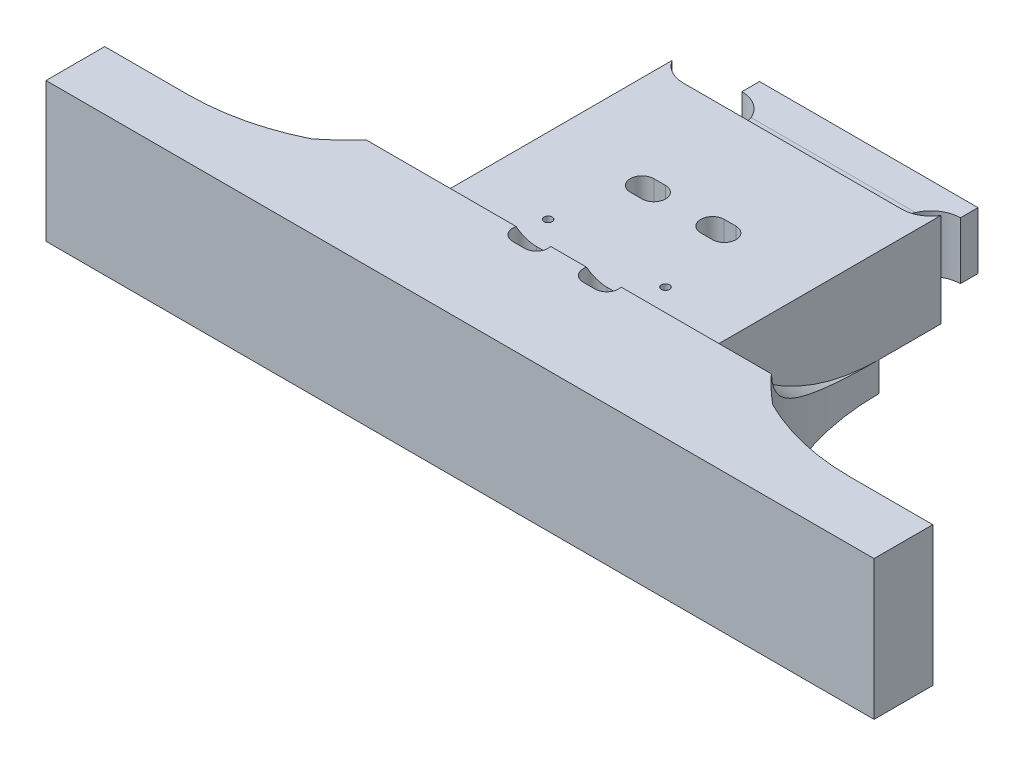
SolidWorks part; units mm, degrees
ref_plane "Front Plane" through (0, 0, 0) normal (0, 0, 1) x (1, 0, 0)
ref_plane "Top Plane" through (0, 0, 0) normal (0, 1, 0) x (1, 0, 0)
ref_plane "Right Plane" through (0, 0, 0) normal (1, 0, 0) x (0, 0, -1)
sketch "Sketch2" plane through (0, 0, 138.6086) normal (0, 0, 1) x (1, 0, 0)
  line L0 (70.4445, 0) -> (70.4445, 5) construction
  line L1 (-70.5526, 0) -> (70.4445, 0)
  line L2 (-70.5526, 0) -> (-70.5526, 23.7194)
  line L3 (-70.5526, 23.7194) -> (70.4445, 23.7194)
  line L4 (70.4445, 0) -> (70.4445, 23.7194)
extrude "Boss-Extrude1" add sketch "Sketch2" along normal blind 40
sketch "Sketch3" plane through (-70.5526, 0, 0) normal (-1, 0, 0) x (0, 0, 1)
  line L0 (138.6086, 23.7194) -> (138.6086, 0) construction
  line L3 (138.6086, 5) -> (152.3731, 5)
  line L4 (178.6086, 23.7194) -> (138.6086, 23.7194) construction
  line L5 (158.6086, 23.7194) -> (178.6086, 23.7194)
  line L8 (138.6086, 23.7194) -> (138.6086, 0)
  line L9 (138.6086, 0) -> (178.6086, 0)
  line L10 (178.6086, 0) -> (178.6086, 23.7194)
  line L11 (178.6086, 23.7194) -> (138.6086, 23.7194)
  line L12 (138.6086, 23.7194) -> (138.6086, 0)
  line L13 (138.6086, 0) -> (178.6086, 0)
  line L14 (178.6086, 0) -> (178.6086, 23.7194)
  line L15 (178.6086, 23.7194) -> (138.6086, 23.7194)
  arc A0 (138.6086, 5) -> (168.6086, 23.7194) centre (138.6086, 38.399) ccw
  point P2 (158.6086, 23.7194)
  point P21 (168.6086, 23.7194)
  line M6 (138.6086, 23.7194) -> (138.6086, 0)
  line M9 (178.6086, 23.7194) -> (138.6086, 23.7194)
  dimension "D2" = 5
  dimension "D3" = 23.7194
  dimension "D1" = 0
extrude "Cut-Extrude1" cut sketch "Sketch3" against normal through all contours M6 M9 region at (-70.5526, 16.0164, 150.4428)
sketch "Sketch4" plane through (0, 5, 0) normal (0, 1, 0) x (1, 0, 0)
  line L0 (-0.0541, -138.6086) -> (-0.0541, -183.6086)
  line L1 (70.4445, -138.6086) -> (-70.5526, -138.6086) construction
  line L2 (70.4445, -168.6086) -> (-70.5526, -168.6086) construction
  line L4 (-22.9249, -168.6086) -> (-22.9249, -128.1086)
  line L9 (-0.6345, -168.6086) -> (0.8576, -168.6086) construction
  line L10 (22.8168, -168.6086) -> (-22.9249, -168.6086)
  line L11 (22.8168, -168.6086) -> (22.8168, -128.1086)
  line L15 (-18.6541, -120.5086) -> (-18.6541, -117.5086)
  line L16 (-0.0541, -138.6086) -> (-0.0541, -118.0787) construction
  line L17 (-18.6541, -117.5086) -> (18.5459, -117.5086)
  line L19 (18.5459, -120.5086) -> (18.5459, -117.5086)
  circle A5 centre (18.5459, -125.5086) radius 5 construction
  arc A7 (18.5459, -120.5086) -> (22.8168, -128.1086) centre (18.5459, -125.5086) ccw
  circle A9 centre (-18.6541, -125.5086) radius 5
  arc A10 (-22.9249, -128.1086) -> (-18.6541, -120.5086) centre (-18.6541, -125.5086) ccw
  circle A11 centre (18.5459, -125.5086) radius 5
  arc A12 (18.5459, -120.5086) -> (22.8168, -128.1086) centre (18.5459, -125.5086) ccw
  point P31 (-0.0541, -117.5086)
  line M11 (-13.4387, -138.6086) -> (13.3306, -138.6086)
  arc M12 (13.3306, -138.6086) -> (8.0264, -116.1199) centre (18.5459, -125.5086) cw
  dimension "D3" = 3
  dimension "D1" = 0
  dimension "D4" = 0
extrude "Boss-Extrude2" add sketch "Sketch4" along normal blind 16 contours L17 M11 M12 | A7 L19 L17 L0 L10 L11 M12 M11 | A10 L4 L10 L0 L17 L15 M11 region at (11.7773, 5, 146.7916) region at (-9.2774, 5, 142.9696)
sketch "Sketch6" plane through (0, 23.7194, 0) normal (0, 1, 0) x (1, 0, 0)
  line L0 (-18.6541, -130.5086) -> (18.5459, -130.5086)
  line L1 (18.5459, -120.5086) -> (18.5459, -117.5086) construction
  line L2 (-18.6541, -117.5086) -> (18.5459, -117.5086) construction
  line L3 (-18.6541, -120.5086) -> (-18.6541, -117.5086) construction
  line L4 (18.5459, -117.5086) -> (18.5459, -120.5086)
  line L5 (-18.6541, -117.5086) -> (-18.6541, -120.5086)
  line L6 (18.5459, -117.5086) -> (-18.6541, -117.5086)
  arc A2 (18.5459, -120.5086) -> (22.8168, -128.1086) centre (18.5459, -125.5086) ccw construction
  arc A3 (-22.9249, -128.1086) -> (-18.6541, -120.5086) centre (-18.6541, -125.5086) ccw
  arc A4 (18.5459, -120.5086) -> (22.8168, -128.1086) centre (18.5459, -125.5086) ccw
  arc A5 (-22.9249, -128.1086) -> (-18.6541, -120.5086) centre (-18.6541, -125.5086) ccw construction
extrude "Cut-Extrude2" cut sketch "Sketch6" against normal blind 9 contours L0 region at (-0.0541, 23.7194, 123.7178)
fillet "Fillet1" radius 7 1 edges at (-0.0541, 14.7194, 130.5086)
sketch "Sketch10" plane through (0, 21, 0) normal (0, 1, 0) x (1, 0, 0)
  line L1 (-22.9249, -138.6086) -> (-22.9249, -167.1177) construction
  line L2 (-70.5526, -172.1086) -> (70.4445, -172.1086)
  line L3 (70.4445, -178.6086) -> (70.4445, -168.6086) construction
  line L4 (-70.5526, -168.6086) -> (-70.5526, -178.6086) construction
  line L5 (-0.0541, -167.1177) -> (-0.0541, -140.3068) construction
  line L6 (22.8168, -167.1177) -> (-22.9249, -167.1177) construction
  line L7 (70.4445, -168.6086) -> (70.4445, -178.6086)
  line L8 (70.4445, -178.6086) -> (-70.5526, -178.6086)
  line L9 (70.4445, -178.6086) -> (-70.5526, -178.6086) construction
  line L10 (-70.5526, -168.6086) -> (-70.5526, -178.6086)
  line L12 (-70.5526, -178.6086) -> (70.4445, -178.6086) construction
  line L13 (-22.9249, -138.6086) -> (-70.5526, -138.6086) construction
  line L16 (-70.5526, -138.6086) -> (-70.5526, -168.6086) construction
  line L17 (70.4445, -168.6086) -> (70.4445, -138.6086) construction
  line L18 (70.4445, -138.6086) -> (22.8168, -138.6086) construction
  line L19 (22.8168, -167.1177) -> (22.8168, -138.6086) construction
  line L20 (18.5459, -130.5086) -> (-18.6541, -130.5086) construction
  line L21 (-22.9249, -128.1086) -> (-22.9249, -167.1177) construction
  line L22 (22.8168, -167.1177) -> (22.8168, -128.1086) construction
  line L23 (70.4445, -178.6086) -> (70.4445, -168.6086)
  line L24 (-70.5526, -168.6086) -> (-70.5526, -178.6086)
  line L25 (-70.5526, -178.6086) -> (70.4445, -178.6086)
  line L26 (-22.9249, -138.6086) -> (-22.9249, -167.1177)
  line L27 (-22.9249, -138.6086) -> (-70.5526, -138.6086)
  line L28 (-70.5526, -138.6086) -> (-70.5526, -168.6086)
  line L29 (70.4445, -168.6086) -> (70.4445, -138.6086)
  line L30 (70.4445, -138.6086) -> (22.8168, -138.6086)
  line L31 (22.8168, -167.1177) -> (22.8168, -138.6086)
  line L32 (18.5459, -130.5086) -> (-18.6541, -130.5086)
  line L33 (-22.9249, -128.1086) -> (-22.9249, -167.1177)
  line L34 (22.8168, -167.1177) -> (22.8168, -128.1086)
  arc A0 (-22.9249, -138.6086) -> (-56.4249, -172.1086) centre (-56.4249, -138.6086) cw
  arc A2 (-22.9249, -128.1086) -> (-18.6541, -130.5086) centre (-18.6541, -125.5086) ccw construction
  arc A3 (18.5459, -130.5086) -> (22.8168, -128.1086) centre (18.5459, -125.5086) ccw construction
  arc A4 (-22.9249, -128.1086) -> (-18.6541, -130.5086) centre (-18.6541, -125.5086) ccw
  arc A5 (18.5459, -130.5086) -> (22.8168, -128.1086) centre (18.5459, -125.5086) ccw
  arc A6 (22.8168, -138.6086) -> (56.3168, -172.1086) centre (56.3168, -138.6086) ccw
  point P19 (-0.0541, -178.6086)
  dimension "D1" = 6.5
extrude "Cut-Extrude3" cut sketch "Sketch10" against normal through all both and the other way through all contours A0 L27 L28 L10 L2 | L30 A6 L2 L7 L29 region at (-49.6421, 21, 153.7111) region at (49.5339, 21, 153.7111)
sketch "Sketch12" plane through (0, 23.7194, 0) normal (0, 1, 0) x (1, 0, 0)
  line L1 (-22.9249, -167.1177) -> (-22.9249, -128.1086) construction
  line L2 (56.3168, -177.1086) -> (70.4445, -177.1086)
  line L3 (56.3168, -177.1086) -> (70.4445, -177.1086)
  line L4 (-70.5526, -177.1086) -> (-56.4249, -177.1086)
  line L5 (-70.5526, -177.1086) -> (-56.4249, -177.1086)
  line L6 (22.8168, -167.1177) -> (22.8168, -128.1086) construction
  line L7 (-22.9249, -167.1177) -> (-22.9249, -128.1086)
  line L8 (22.8168, -167.1177) -> (22.8168, -128.1086)
  line L9 (-70.5526, -178.6086) -> (-70.5526, -172.1086) construction
  line L10 (-70.5526, -172.1086) -> (-56.4249, -172.1086) construction
  line L11 (70.4445, -178.6086) -> (70.4445, -172.1086) construction
  line L12 (56.3168, -172.1086) -> (70.4445, -172.1086) construction
  line L13 (-70.5526, -178.6086) -> (-70.5526, -172.1086)
  line L14 (-70.5526, -172.1086) -> (-56.4249, -172.1086)
  line L15 (70.4445, -178.6086) -> (70.4445, -172.1086)
  line L16 (56.3168, -172.1086) -> (70.4445, -172.1086)
  arc A0 (-22.9249, -138.6086) -> (-39.2918, -173.0863) centre (-67.4227, -138.6086) cw
  arc A1 (22.8168, -138.6086) -> (39.1836, -173.0863) centre (67.3146, -138.6086) ccw
  arc A7 (17.8168, -138.6086) -> (39.1836, -173.0863) centre (56.3168, -138.6086) ccw
  arc A8 (39.1836, -173.0863) -> (56.3168, -177.1086) centre (56.3168, -138.6086) ccw
  arc A10 (39.1836, -173.0863) -> (56.3168, -177.1086) centre (56.3168, -138.6086) ccw
  arc A11 (-56.4249, -172.1086) -> (-41.5169, -168.6086) centre (-56.4249, -138.6086) ccw construction
  arc A12 (-41.5169, -168.6086) -> (-22.9249, -138.6086) centre (-56.4249, -138.6086) ccw construction
  arc A13 (-56.4249, -177.1086) -> (-39.2918, -173.0863) centre (-56.4249, -138.6086) ccw
  arc A14 (-39.2918, -173.0863) -> (-17.9249, -138.6086) centre (-56.4249, -138.6086) ccw
  arc A15 (-56.4249, -177.1086) -> (-39.2918, -173.0863) centre (-56.4249, -138.6086) ccw
  arc A17 (41.4087, -168.6086) -> (56.3168, -172.1086) centre (56.3168, -138.6086) ccw construction
  arc A18 (22.8168, -138.6086) -> (41.4087, -168.6086) centre (56.3168, -138.6086) ccw construction
  arc A19 (-56.4249, -172.1086) -> (-41.5169, -168.6086) centre (-56.4249, -138.6086) ccw
  arc A20 (-41.5169, -168.6086) -> (-22.9249, -138.6086) centre (-56.4249, -138.6086) ccw
  arc A21 (41.4087, -168.6086) -> (56.3168, -172.1086) centre (56.3168, -138.6086) ccw
  arc A22 (22.8168, -138.6086) -> (41.4087, -168.6086) centre (56.3168, -138.6086) ccw
  arc M7 (-41.5169, -168.6086) -> (-56.4249, -172.1086) centre (-56.4249, -138.6086) cw
  line M8 (-56.4249, -172.1086) -> (-70.5526, -172.1086)
  line M9 (-70.5526, -172.1086) -> (-70.5526, -178.6086)
  line M11 (70.4445, -178.6086) -> (70.4445, -172.1086)
  line M12 (70.4445, -172.1086) -> (56.3168, -172.1086)
  arc M13 (56.3168, -172.1086) -> (41.4087, -168.6086) centre (56.3168, -138.6086) cw
  line M14 (41.4087, -168.6086) -> (-41.5169, -168.6086)
  dimension "D1" = 5
  dimension "D2" = 5
extrude "Cut-Extrude4" cut sketch "Sketch12" against normal through all contours A10 L3 M11 M12 M13 M14 | A22 L8 M14 | A15 L5 M14 M7 M8 M9 | A20 L7 M14 region at (53.5528, 23.7194, 173.5934) region at (31.8794, 23.7194, 162.178) region at (-53.6609, 23.7194, 173.5934) region at (-31.9875, 23.7194, 162.178)
sketch "Sketch11" plane through (0, 21, 0) normal (0, 1, 0) x (1, 0, 0)
  line L0 (70.4445, -178.6086) -> (70.4445, -177.1086) construction
  line L1 (-70.5526, -178.6086) -> (70.4445, -178.6086)
  line L2 (-70.5526, -178.6086) -> (-70.5526, -187.1086)
  line L3 (-70.5526, -187.1086) -> (70.4445, -187.1086)
  line L4 (70.4445, -178.6086) -> (70.4445, -187.1086)
  dimension "D1" = 8.5
extrude "Boss-Extrude4" add sketch "Sketch11" along normal up to surface and the other way up to surface up to face at (-0.0541, 23.7194, 175.1199) other way up to face at (-0.0541, 0, 169.4713)
sketch "Sketch14" plane through (0, 21, 0) normal (0, 1, 0) x (1, 0, 0)
  line L0 (-0.0541, -167.1177) -> (-0.0541, -104.4076) construction
  line L1 (22.8168, -167.1177) -> (-22.9249, -167.1177) construction
  circle A0 centre (-10.0541, -162.1177) radius 0.7
  circle A1 centre (9.9459, -162.1177) radius 0.7
  dimension "D1" = 1.4
  dimension "D2" = 20
  dimension "D3" = 5
extrude "Cut-Extrude6" cut sketch "Sketch14" against normal blind 4
sketch "Sketch16" plane through (0, 23.7194, 0) normal (0, 1, 0) x (1, 0, 0)
  line L0 (-0.0541, -187.1086) -> (-0.0541, -112.1551) construction
  line L1 (70.4445, -187.1086) -> (-70.5526, -187.1086) construction
  line L2 (-7.0541, -149.1177) -> (-5.0541, -149.1177) construction
  line L3 (-7.0541, -147.1177) -> (-5.0541, -147.1177)
  line L4 (-7.0541, -151.1177) -> (-5.0541, -151.1177)
  line L5 (-10.0541, -159.1177) -> (14.0991, -159.1177)
  line L6 (6.9459, -149.1177) -> (4.9459, -149.1177) construction
  line L7 (6.9459, -147.1177) -> (4.9459, -147.1177)
  line L8 (6.9459, -151.1177) -> (4.9459, -151.1177)
  line L9 (6.9459, -169.1177) -> (4.9459, -169.1177) construction
  line L10 (6.9459, -171.1177) -> (4.9459, -171.1177)
  line L11 (6.9459, -167.1177) -> (4.9459, -167.1177)
  line L12 (-7.0541, -169.1177) -> (-5.0541, -169.1177) construction
  line L13 (-7.0541, -171.1177) -> (-5.0541, -171.1177)
  line L14 (-7.0541, -167.1177) -> (-5.0541, -167.1177)
  arc A0 (-7.0541, -147.1177) -> (-7.0541, -151.1177) centre (-7.0541, -149.1177) ccw
  arc A1 (-5.0541, -151.1177) -> (-5.0541, -147.1177) centre (-5.0541, -149.1177) ccw
  circle A2 centre (-10.0541, -162.1177) radius 0.7 construction
  circle A3 centre (-10.0541, -162.1177) radius 0.7
  arc A4 (6.9459, -147.1177) -> (6.9459, -151.1177) centre (6.9459, -149.1177) cw
  arc A5 (4.9459, -151.1177) -> (4.9459, -147.1177) centre (4.9459, -149.1177) cw
  arc A6 (6.9459, -171.1177) -> (6.9459, -167.1177) centre (6.9459, -169.1177) ccw
  arc A7 (4.9459, -167.1177) -> (4.9459, -171.1177) centre (4.9459, -169.1177) ccw
  arc A8 (-7.0541, -171.1177) -> (-7.0541, -167.1177) centre (-7.0541, -169.1177) cw
  arc A9 (-5.0541, -167.1177) -> (-5.0541, -171.1177) centre (-5.0541, -169.1177) cw
  point P6 (-6.0541, -149.1177)
  point P18 (5.9459, -149.1177)
  point P25 (5.9459, -169.1177)
  point P32 (-6.0541, -169.1177)
  point P37 (0, 0)
  line M17 (34.4504, -168.6086) -> (-34.5585, -168.6086)
  dimension "D2" = 2
  dimension "D1" = 2
  dimension "D3" = 10
  dimension "D4" = 3
  dimension "D5" = 12
extrude "Cut-Extrude7" cut sketch "Sketch16" against normal through all contours L4 A1 L3 A0 | A5 L8 A4 L7 | A7 L10 A6 M17 | L11 A7 A6 M17 | A9 L14 A8 M17 | A9 A8 L13 M17 region at (-6.0541, 23.7194, 149.1177) region at (5.9459, 23.7194, 149.1177) region at (-6.0541, 23.7194, 169.7609) region at (-6.0541, 23.7194, 167.9366) region at (5.9459, 23.7194, 169.7609) region at (5.9459, 23.7194, 167.9366)
